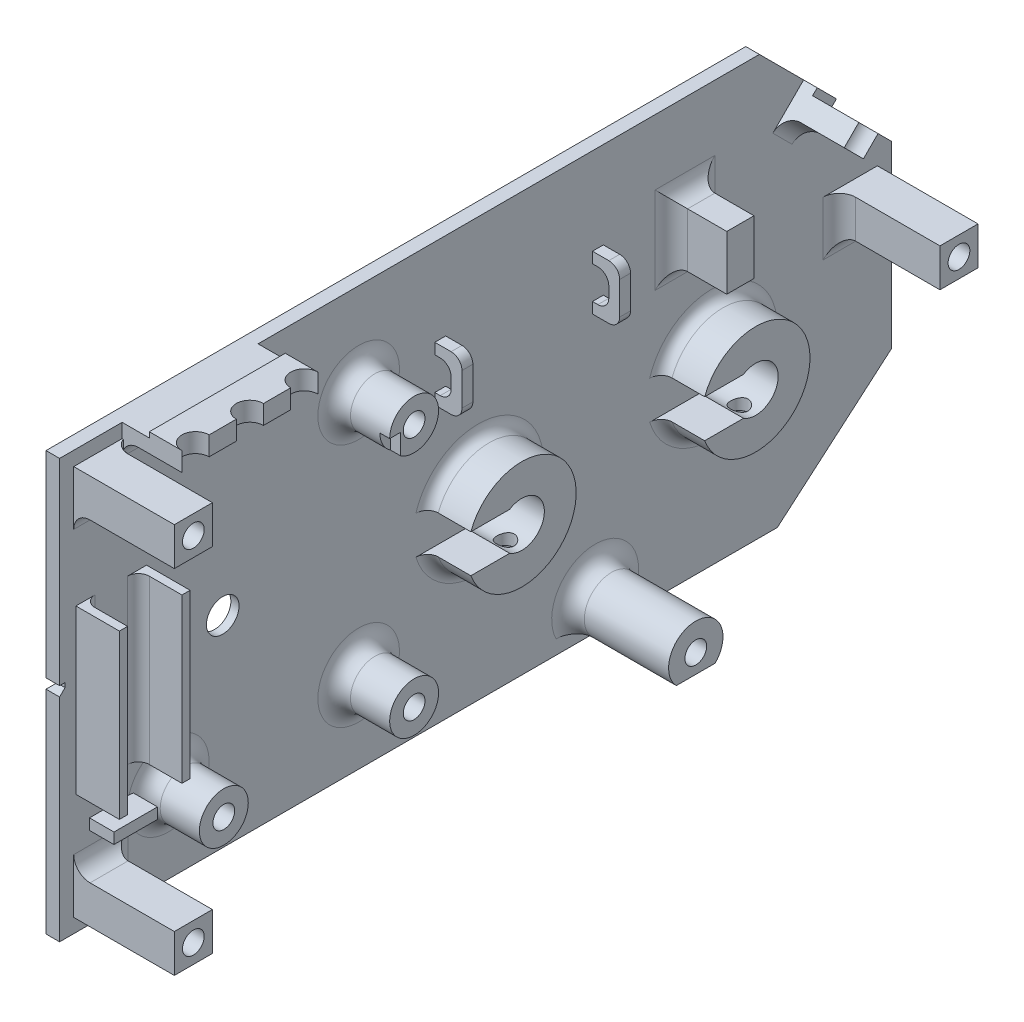
SolidWorks part; units mm, degrees
ref_plane "Front Plane" through (0, 0, 0) normal (0, 0, 1) x (1, 0, 0)
ref_plane "Top Plane" through (0, 0, 0) normal (0, 1, 0) x (1, 0, 0)
ref_plane "Right Plane" through (0, 0, 0) normal (1, 0, 0) x (0, 0, -1)
sketch "Sketch1" plane through (0, 0, 0) normal (1, 0, 0) x (0, 0, -1)
  line L0 (0, 0) -> (0, 77)
  line L1 (0, 77) -> (127, 77)
  line L2 (127, 77) -> (153, 51)
  line L3 (153, 51) -> (153, 18)
  line L4 (153, 18) -> (132, 0)
  line L5 (132, 0) -> (0, 0)
  dimension "D1" = 132
  dimension "D2" = 77
  dimension "D3" = 26
  dimension "D4" = 26
  dimension "D5" = 153
  dimension "D6" = 18
extrude "Base" add sketch "Sketch1" along normal blind 2.5
ref_plane "Middle" through (13.5, 0, 0) normal (1, 0, 0) x (0, 0, -1)
sketch "Sketch2" plane through (2.5, 0, 0) normal (1, 0, 0) x (0, 0, -1)
  line L1 (112.5, 62) -> (117.5, 62)
  line L2 (112.5, 62) -> (112.5, 52)
  line L3 (112.5, 52) -> (117.5, 52)
  line L4 (117.5, 62) -> (117.5, 52)
  line L5 (112.5, 62) -> (117.5, 52) construction
  line L6 (112.5, 52) -> (117.5, 62) construction
  circle A0 centre (20, 15) radius 4.5
  circle A1 centre (55, 15) radius 4.5
  circle A2 centre (55, 60) radius 4.5
  circle A3 centre (20, 15) radius 2
  circle A4 centre (55, 15) radius 2
  circle A5 centre (55, 60) radius 2
  point P9 (115, 57)
  dimension "D1" = 9
  dimension "D2" = 4
  dimension "D3" = 20
  dimension "D4" = 15
  dimension "D5" = 55
  dimension "D6" = 60
  dimension "D7" = 55
  dimension "D8" = 115
  dimension "D9" = 57
  dimension "D10" = 10
  dimension "D11" = 5
extrude "PCB_Mount" add sketch "Sketch2" along normal blind 10.2
sketch "Sketch24" plane through (12.7, 0, 0) normal (1, 0, 0) x (0, 0, -1)
  circle A0 centre (55, 60) radius 2 construction
  circle A1 centre (55, 15) radius 2 construction
  circle A2 centre (20, 15) radius 2 construction
  circle A3 centre (55, 60) radius 2
  circle A4 centre (55, 15) radius 2
  circle A5 centre (20, 15) radius 2
extrude "Boss-Extrude14" add sketch "Sketch24" against normal up to next from offset 8.5 offset against normal yes
fillet "Fillet2" radius 3 7 edges at (2.5, 62, -115) (2.5, 57, -117.5) (2.5, 52, -115) (2.5, 57, -112.5) (2.5, 60, -50.5) (2.5, 15, -15.5) (2.5, 15, -50.5)
sketch "Sketch30" plane through (12.7, 0, 0) normal (1, 0, 0) x (0, 0, -1)
  line L2 (52.5, 56.2583) -> (52.5, 60)
  line L3 (52.5, 60) -> (50.5, 60)
  arc A3 (50.5, 60) -> (52.5, 56.2583) centre (55, 60) ccw
  circle A4 centre (55, 60) radius 4.5 construction
  dimension "D1" = 2.5
  dimension "D2" = 0
extrude "Cut-Extrude12" cut sketch "Sketch30" against normal blind 1.8
ref_plane "Plane1" through (0, 32, 0) normal (0, 1, 0) x (1, 0, 0)
sketch "Sketch3" plane through (2.5, 0, 0) normal (1, 0, 0) x (0, 0, -1)
  line L0 (5.775, 32) -> (-5.775, 32) construction
  circle A0 centre (77, 32) radius 4.15
  circle A1 centre (120, 32) radius 4.15
  circle A2 centre (77, 32) radius 10
  circle A3 centre (120, 32) radius 10
  dimension "D3" = 8.3
  dimension "D4" = 20
  dimension "D1" = 77
  dimension "D2" = 120
extrude "Boss-Extrude3" add sketch "Sketch3" along normal blind 8
sketch "Sketch4" plane through (10.5, 0, 0) normal (1, 0, 0) x (0, 0, -1)
  line L1 (74.7701, 35.5) -> (67, 35.5)
  line L2 (74.7701, 35.5) -> (74.7701, 28.5)
  line L3 (74.7701, 28.5) -> (67, 28.5)
  line L4 (67, 35.5) -> (67, 28.5)
  line L5 (117.7701, 35.5) -> (110, 35.5)
  line L6 (117.7701, 35.5) -> (117.7701, 28.5)
  line L7 (117.7701, 28.5) -> (110, 28.5)
  line L8 (110, 35.5) -> (110, 28.5)
  circle A0 centre (77, 32) radius 4.15 construction
  circle A1 centre (77, 32) radius 10 construction
  circle A2 centre (120, 32) radius 4.15 construction
  circle A3 centre (120, 32) radius 10 construction
  dimension "D1" = 7
extrude "Cut-Extrude1" cut sketch "Sketch4" against normal blind 8
ref_axis "Axis1" through (10.5, 32, -77) along (-1, 0, 0)
ref_axis "Axis2" through (10.5, 32, -120) along (-1, 0, 0)
sketch "Sketch5" plane through (0, 32, 0) normal (0, 1, 0) x (1, 0, 0)
  line L2 (10.5, 77) -> (2.5, 77) construction
  line L3 (10.5, 120) -> (2.5, 120) construction
  line L4 (10.5, 67.6325) -> (10.5, 87) construction
  circle A0 centre (7.5, 77) radius 1.6
  circle A1 centre (7.5, 120) radius 1.6
  dimension "D1" = 3.2
  dimension "D2" = 3
extrude "Cut-Extrude2" cut sketch "Sketch5" against normal through all
sketch "Sketch27" plane through (0, 32, 0) normal (0, 1, 0) x (1, 0, 0)
  circle A0 centre (7.5, 77) radius 2
  circle A1 centre (7.5, 120) radius 2
  dimension "D1" = 4
extrude "Cut-Extrude7" cut sketch "Sketch27" against normal up to next from offset 6 offset against normal yes
fillet "Fillet3" radius 2 2 edges at (2.5, 32, -130) (2.5, 32, -87)
sketch "Sketch13" plane through (0, 77, 0) normal (0, 1, 0) x (1, 0, 0)
  line L1 (13.5, 11.5) -> (2.5, 11.5)
  line L2 (13.5, 11.5) -> (13.5, 36.5)
  line L3 (13.5, 36.5) -> (2.5, 36.5)
  line L4 (2.5, 11.5) -> (2.5, 36.5)
  line L5 (13.5, 11.5) -> (2.5, 36.5) construction
  line L6 (13.5, 36.5) -> (2.5, 11.5) construction
  line L7 (2.5, 127) -> (2.5, 0) construction
  line L8 (13.5, -42.35) -> (13.5, 42.35) construction
  point P0 (8, 24)
  dimension "D1" = 24
  dimension "D2" = 25
extrude "Boss-Extrude8" add sketch "Sketch13" against normal blind 2.5
sketch "Sketch15" plane through (0, 77, 0) normal (0, 1, 0) x (1, 0, 0)
  line L0 (13.5, 11.5) -> (13.5, 36.5) construction
  line L1 (13.5, 11.5) -> (7.5, 11.5)
  line L2 (13.5, 11.5) -> (13.5, 36.5)
  line L3 (13.5, 36.5) -> (7.5, 36.5)
  line L4 (7.5, 11.5) -> (7.5, 36.5)
  point P6 (13.5, 24)
  point P7 (13.5, 24)
  dimension "D1" = 6
  dimension "D2" = 25
extrude "Boss-Extrude9" add sketch "Sketch15" along normal blind 1 and the other way blind 2.5
sketch "Sketch16" plane through (0, 78, 0) normal (0, 1, 0) x (1, 0, 0)
  line L0 (13.5, 11.5) -> (13.5, 36.5) construction
  circle A0 centre (13.5, 24) radius 2.5
  circle A1 centre (13.5, 34) radius 2.5
  circle A2 centre (13.5, 14) radius 2.5
  dimension "D3" = 5
  dimension "D1" = 10
  dimension "D2" = 10
extrude "Cut-Extrude4" cut sketch "Sketch16" against normal up to next
sketch "Sketch9" plane through (0, 0, 0) normal (-1, 0, 0) x (0, 0, 1)
  line L0 (-127, 77) -> (-128.6971, 77)
  line L1 (-128.6971, 77) -> (-140.3643, 65.3327)
  line L2 (-140.3643, 65.3327) -> (-139.5158, 64.4842)
  line L3 (-153, 51) -> (-127, 77) construction
  line L4 (-139.5158, 64.4842) -> (-127, 77)
  dimension "D1" = 1.2
  dimension "D2" = 16.5
extrude "Boss-Extrude5" add sketch "Sketch9" against normal up to vertex (2.5 mm away) up to point (2.5, 77, -127)
sketch "Sketch10" plane through (2.5, 0, 0) normal (1, 0, 0) x (0, 0, -1)
  line L0 (140.3643, 65.3327) -> (136.8288, 68.8683)
  line L1 (140.3643, 65.3327) -> (136.8288, 61.7972)
  line L2 (136.8288, 68.8683) -> (133.2933, 65.3327)
  line L3 (136.8288, 61.7972) -> (133.2933, 65.3327)
  line L4 (128.6971, 77) -> (140.3643, 65.3327) construction
  dimension "D1" = 5
  dimension "D2" = 5
extrude "Boss-Extrude6" add sketch "Sketch10" along normal blind 2.5
sketch "Sketch12" plane through (0, 99.313, -99.313) normal (0, -0.7071, 0.7071) x (1, 0, 0)
  line L0 (5, -48.0553) -> (5, -53.0553)
  line L1 (5, -48.0553) -> (13.5, -48.0553)
  line L2 (5, -53.0553) -> (13.5, -53.0553)
  line L4 (0, -72.1249) -> (0, -53.0553) construction
  arc A0 (13.5, -48.0553) -> (13.5, -53.0553) centre (13.5, -50.5553) ccw
  dimension "D1" = 2.5
  dimension "D2" = 13.5
extrude "Boss-Extrude7" add sketch "Sketch12" along direction (0, -0.7071, 0.7071) on the side against the normal up to surface (3.8 mm away) up to face at (1.25, 57.7421, -146.2579)
fillet "Fillet4" radius 3 2 edges at (2.5, 63.565, -135.061) (2.5, 74.5, -24)
sketch "Sketch19" plane through (2.5, 0, 0) normal (1, 0, 0) x (0, 0, -1)
  line L0 (0, 77) -> (0, 0) construction
  line L1 (3, 52) -> (4.5, 52)
  line L2 (3, 52) -> (3, 22)
  line L3 (3, 22) -> (4.5, 22)
  line L4 (4.5, 52) -> (4.5, 22)
  line L6 (14.5, 52) -> (16, 52)
  line L7 (14.5, 52) -> (14.5, 22)
  line L8 (14.5, 22) -> (16, 22)
  line L9 (16, 52) -> (16, 22)
  dimension "D1" = 3
  dimension "D2" = 1.5
  dimension "D3" = 22
  dimension "D4" = 30
  dimension "D5" = 10
extrude "Boss-Extrude11" add sketch "Sketch19" along normal blind 8
fillet "Fillet1" radius 2 2 edges at (2.5, 37, -4.5) (2.5, 37, -14.5)
sketch "Sketch20" plane through (2.5, 0, 0) normal (1, 0, 0) x (0, 0, -1)
  line L0 (3, 22) -> (16, 22) construction
  line L3 (5.5, 15) -> (13.5, 15)
  line L4 (5.5, 15) -> (5.5, 17)
  line L5 (5.5, 17) -> (13.5, 17)
  line L6 (13.5, 15) -> (13.5, 17)
  line L7 (5.5, 15) -> (13.5, 17) construction
  line L8 (5.5, 17) -> (13.5, 15) construction
  point P5 (9.5, 16)
  point P10 (9.5, 22)
  dimension "D1" = 15
  dimension "D2" = 2
  dimension "D3" = 8
extrude "Boss-Extrude12" add sketch "Sketch20" along normal blind 4.5
sketch "Sketch21" plane through (2.5, 0, 0) normal (1, 0, 0) x (0, 0, -1)
  line L0 (11.5, 77) -> (0, 77) construction
  line L1 (2.6, 74.4) -> (9.6, 74.4)
  line L2 (2.6, 74.4) -> (2.6, 67.4)
  line L3 (2.6, 67.4) -> (9.6, 67.4)
  line L4 (9.6, 74.4) -> (9.6, 67.4)
  line L5 (2.6, 2.6) -> (9.6, 2.6)
  line L6 (2.6, 2.6) -> (2.6, 9.6)
  line L7 (2.6, 9.6) -> (9.6, 9.6)
  line L8 (9.6, 2.6) -> (9.6, 9.6)
  line L13 (150.4, 48.4) -> (143.4, 48.4)
  line L14 (150.4, 48.4) -> (150.4, 41.4)
  line L15 (150.4, 41.4) -> (143.4, 41.4)
  line L16 (143.4, 48.4) -> (143.4, 41.4)
  line L17 (153, 18) -> (153, 51) construction
  line L18 (102.0707, 2.6) -> (94.9293, 2.6)
  line L19 (0, 0) -> (132, 0) construction
  arc A0 (102.0707, 2.6) -> (94.9293, 2.6) centre (98.5, 6.1) ccw
  point P10 (9.6, 6.1)
  dimension "D8" = 10
  dimension "D1" = 2.6
  dimension "D2" = 2.6
  dimension "D3" = 2.6
  dimension "D4" = 2.6
  dimension "D6" = 2.6
  dimension "D7" = 7
  dimension "D5" = 98.5
  dimension "D9" = 2.6
extrude "Boss-Extrude13" add sketch "Sketch21" along normal blind 18.5
sketch "Sketch22" plane through (21, 0, 0) normal (1, 0, 0) x (0, 0, -1)
  line L0 (2.6, 9.6) -> (9.6, 2.6) construction
  line L2 (143.4, 48.4) -> (150.4, 41.4) construction
  line L3 (2.6, 74.4) -> (9.6, 67.4) construction
  circle A0 centre (6.1, 6.1) radius 2
  circle A1 centre (6.1, 70.9) radius 2
  circle A2 centre (146.9, 44.9) radius 2
  circle A3 centre (98.5, 6.1) radius 2
  circle A4 centre (98.5, 6.1) radius 5 construction
  point P6 (6.1, 6.1)
  dimension "D1" = 4
extrude "Cut-Extrude5" cut sketch "Sketch22" against normal blind 7
sketch "Sketch25" plane through (0, 0, 0) normal (-1, 0, 0) x (0, 0, 1)
  circle A0 centre (-30, 37) radius 3
  dimension "D3" = 6
  dimension "D1" = 30
  dimension "D2" = 37
extrude "Cut-Extrude6" cut sketch "Sketch25" against normal up to next
fillet "Fillet5" radius 3 7 edges at (2.5, 11.1, -98.5) (2.5, 44.9, -143.4) (2.5, 41.4, -146.9) (2.5, 70.9, -9.6) (2.5, 67.4, -6.1) (2.5, 9.6, -6.1) (2.5, 6.1, -9.6)
sketch "Sketch28" plane through (0, 0, 0) normal (-1, 0, 0) x (0, 0, 1)
  line L3 (0, 77) -> (0, 0) construction
  line L4 (-27.6676, 40) -> (0, 40)
  line L11 (0, 40.8) -> (0, 40)
  line L12 (-51.1941, 40.8) -> (0, 40.8)
  line L13 (-78.8256, 64.4842) -> (-51.1941, 40.8)
  line L14 (-144.5158, 64.4842) -> (-78.8256, 64.4842)
  line L15 (-144.5158, 63.6842) -> (-144.5158, 64.4842)
  line L16 (-51.49, 40) -> (-32.3324, 40)
  line L17 (-79.1216, 63.6842) -> (-51.49, 40)
  line L18 (-144.5158, 63.6842) -> (-79.1216, 63.6842)
  arc A0 (-32.3324, 40) -> (-27.6676, 40) centre (-30, 37) ccw
  dimension "D3" = 5
  dimension "D1" = 0.8
  dimension "D2" = 0.8
  dimension "D4" = 40
  dimension "D5" = 139.399
  dimension "D6" = 51.49
extrude "Cut-Extrude10" cut sketch "Sketch28" against normal blind 1
sketch "Sketch29" plane through (0, 0, 0) normal (0, 0, 1) x (1, 0, 0)
  line L0 (2.5, 77) -> (2.5, 0) construction
  line L1 (1, 40.8) -> (2.5, 40.8)
  line L2 (1, 40.8) -> (1, 40)
  line L3 (1, 40) -> (2.5, 40)
  line L4 (2.5, 40.8) -> (2.5, 40)
extrude "Cut-Extrude11" cut sketch "Sketch29" against normal blind 1
chamfer "Chamfer1" distance 1 angle 45 6 edges at (0, 63.6842, -109.7187) (0, 51.8421, -65.3058) (0, 40, -41.9112) (0, 33.2, -30) (0, 40, -13.8338) (1.25, 40, 0)
sketch "Sketch31" plane through (2.5, 0, 0) normal (1, 0, 0) x (0, 0, -1)
  line L0 (69, 53) -> (69, 51)
  line L1 (69, 61) -> (71, 61)
  line L2 (69, 61) -> (69, 59)
  line L3 (69, 51) -> (71, 51)
  line L4 (71, 61) -> (71, 59)
  line L5 (69, 61) -> (71, 51) construction
  line L6 (69, 51) -> (71, 61) construction
  line L7 (69, 53) -> (71, 53)
  line L9 (69, 59) -> (71, 59)
  line L11 (69, 53) -> (71, 59) construction
  line L12 (69, 59) -> (71, 53) construction
  line L13 (71, 53) -> (71, 51)
  line L14 (98, 61) -> (100, 61)
  line L15 (100, 61) -> (100, 59)
  line L16 (98, 59) -> (100, 59)
  line L17 (98, 61) -> (98, 59)
  line L18 (98, 51) -> (100, 51)
  line L19 (100, 53) -> (100, 51)
  line L20 (98, 53) -> (100, 53)
  line L21 (98, 53) -> (98, 51)
  point P0 (70, 56)
  point P5 (70, 56)
  dimension "D1" = 2
  dimension "D2" = 2
  dimension "D3" = 10
  dimension "D4" = 56
  dimension "D5" = 70
  dimension "D7" = 27
  dimension "D6" = 2
extrude "Boss-Extrude15" add sketch "Sketch31" along normal blind 3
sketch "Sketch32" plane through (5.5, 0, 0) normal (1, 0, 0) x (0, 0, -1)
  line L0 (71, 51) -> (71, 53) construction
  line L1 (69, 61) -> (71, 61)
  line L2 (69, 61) -> (69, 51)
  line L3 (69, 51) -> (71, 51)
  line L4 (71, 61) -> (71, 51)
  line L5 (69, 51) -> (71, 51) construction
  line L6 (100, 61) -> (98, 61) construction
  line L7 (98, 61) -> (100, 61)
  line L8 (98, 61) -> (98, 51)
  line L9 (98, 51) -> (100, 51)
  line L10 (100, 61) -> (100, 51)
  line L11 (98, 61) -> (98, 59) construction
extrude "Boss-Extrude16" add sketch "Sketch32" along normal blind 2
fillet "Fillet6" radius 2 8 edges at (7.5, 51, -70) (7.5, 51, -99) (7.5, 61, -99) (7.5, 61, -70) (5.5, 53, -99) (5.5, 59, -99) (5.5, 59, -70) (5.5, 53, -70)
equation "\"D2@Sketch16\"=\"D1@Sketch16\""
equation "\"D1@Sketch21\"=\"D2@Sketch21\""
equation "\"D3@Sketch21\"=\"D2@Sketch21\""
equation "\"D4@Sketch21\"=\"D2@Sketch21\""
equation "\"D6@Sketch21\"=\"D2@Sketch21\""
equation "\"D2@Sketch28\"=\"D1@Sketch28\""
